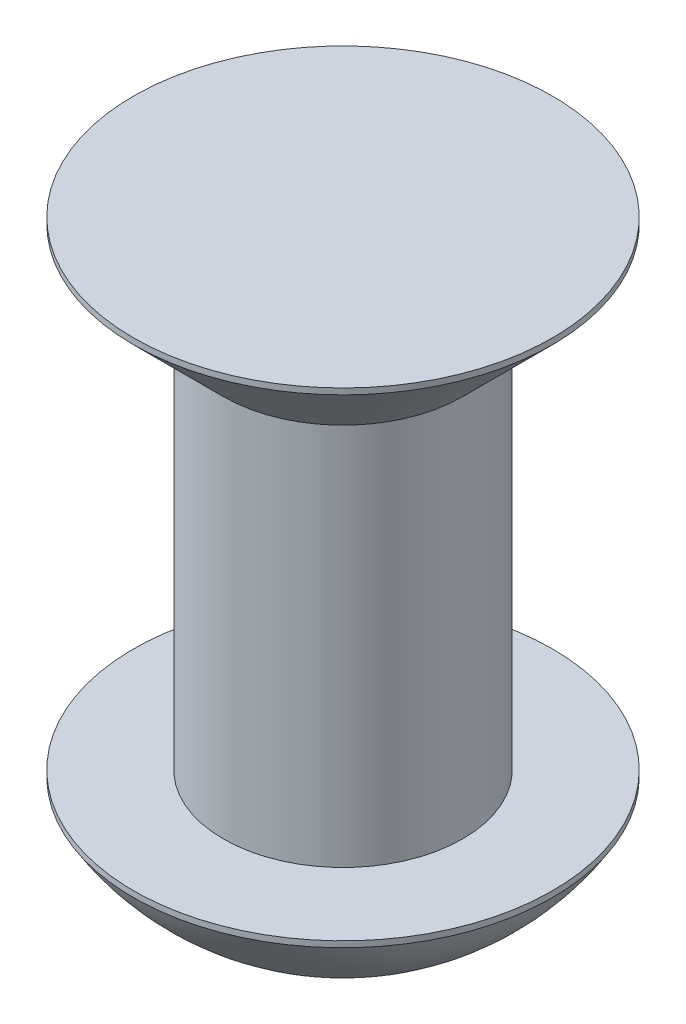
SolidWorks part; units mm, degrees
ref_plane "Спереди" through (0, 0, 0) normal (0, 0, 1) x (1, 0, 0)
ref_plane "Сверху" through (0, 0, 0) normal (0, 1, 0) x (1, 0, 0)
ref_plane "Справа" through (0, 0, 0) normal (1, 0, 0) x (0, 0, -1)
sketch "Эскиз1" plane through (0, 0, 0) normal (0, 0, 1) x (1, 0, 0)
  line L0 (0, 11.284) -> (0, -3.3852) construction
  line L1 (0, 0) -> (1.6, 0)
  line L2 (2, 0.4) -> (2, 6)
  line L3 (2, 6) -> (3.5, 7.5)
  line L4 (3.5, 7.5) -> (3.5, 7.6)
  line L5 (3.5, 7.6) -> (0, 7.6)
  line L6 (0, 0) -> (0, 7.6)
  arc A0 (2, 0.4) -> (1.6, 0) centre (1.6, 0.4) cw
  point P11 (2, 0)
  dimension "D1" = 0.4
  dimension "dm" = 4
  dimension "L" = 6
  dimension "D" = 7
  dimension "D4" = 45
  dimension "k" = 1.6
revolve "Основание-Повернуть" add sketch "Эскиз1" angle 360 about L0
sketch "Эскиз2" plane through (0, 0, 0) normal (0, -1, 0) x (1, 0, 0)
  circle A0 centre (0, 0) radius 2 construction
  circle A1 centre (0, 0) radius 2
extrude "Вытянуть1" add sketch "Эскиз2" against normal blind 2 and the other way offset from surface 8 other way up to face at (0, 7.6, 3.5)
sketch "Эскиз3" plane through (0, -0.4, 0) normal (0, -1, 0) x (1, 0, 0)
  circle A0 centre (0, 0) radius 3.5
extrude "Вытянуть2" add sketch "Эскиз3" along normal blind 0.1
dome "Купол1" faces to dome 1 distance 2 reverse direction no elliptical dome no face at (0, -0.5, -3.5) parameters "D1"=2
equation "\"D1@Эскиз1\"=(\"dm@Эскиз1\"/10)"
